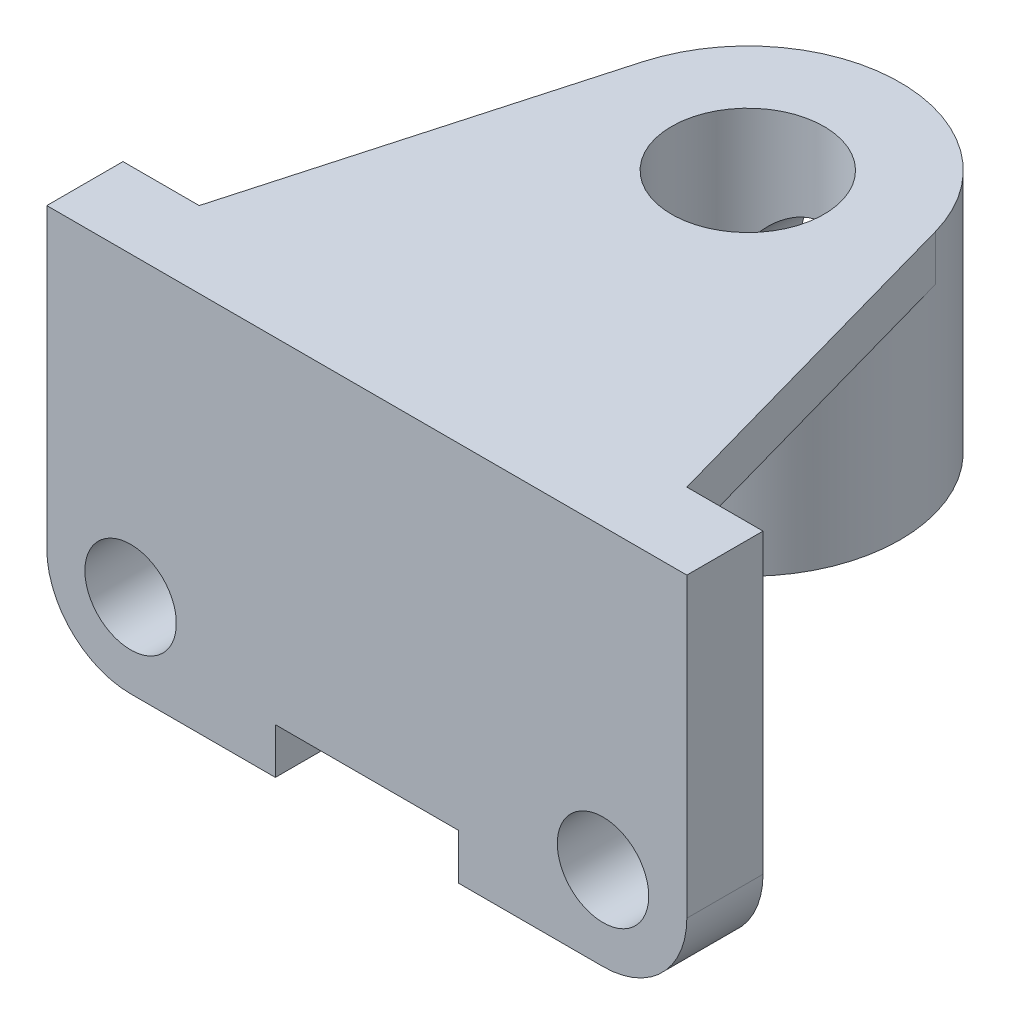
SolidWorks part; units mm, degrees
note: The reader was unsure of these and kept them because the rebuilt part matched: shared geometry of "草图2<3>".
ref_plane "前视基准面" through (0, 0, 0) normal (0, 0, 1) x (1, 0, 0)
ref_plane "上视基准面" through (0, 0, 0) normal (0, 1, 0) x (1, 0, 0)
ref_plane "右视基准面" through (0, 0, 0) normal (1, 0, 0) x (0, 0, -1)
other "Configuration Table"
sketch "草图1" plane through (0, 0, 0) normal (0, 0, 1) x (1, 0, 0)
  line L0 (0, 0) -> (0, -65.1314) construction
  line L1 (-31, -50) -> (-12, -50)
  line L2 (-42, -39) -> (-42, 0)
  line L3 (-42, 0) -> (42, 0)
  line L4 (42, -39) -> (42, 0)
  line L5 (12, -50) -> (31, -50)
  line L7 (-12, -50) -> (-12, -44)
  line L8 (-12, -44) -> (12, -44)
  line L9 (12, -50) -> (12, -44)
  arc A1 (31, -50) -> (42, -39) centre (31, -39) ccw
  arc A2 (-31, -50) -> (-42, -39) centre (-31, -39) cw
  circle A3 centre (31, -39) radius 6
  circle A4 centre (-31, -39) radius 6
  point P9 (42, -50)
  point P12 (-42, -50)
  dimension "D1" = 11
  dimension "D4" = 12
  dimension "D5" = 24
  dimension "D2" = 50
  dimension "D3" = 84
  dimension "D6" = 6
extrude "凸台-拉伸1" add sketch "草图1" along normal blind 10
sketch "草图2" plane through (0, 0, 0) normal (0, 1, 0) x (1, 0, 0)
  line L0 (0, 0) -> (0, 49.8021) construction
  line L1 (32, 0) -> (19.2559, 45.4047)
  line L2 (12, 0) -> (31, 0) construction
  line L3 (-32, 0) -> (-19.2559, 45.4047)
  line L4 (-12, 0) -> (12, 0) construction
  line L5 (-31, 0) -> (-12, 0) construction
  line L6 (12, 0) -> (32, 0)
  line L7 (-12, 0) -> (12, 0)
  line L8 (-32, 0) -> (-12, 0)
  line L9 (12, -10) -> (31, -10) construction
  line L10 (13.2288, 55) -> (-13.2288, 55)
  line L12 (3, 20.2263) -> (3, 0)
  line L13 (3, 0) -> (-3, 0)
  line L14 (-3, 20.2263) -> (-3, 0)
  circle A0 centre (0, 40) radius 10
  arc A1 (3, 20.2263) -> (-3, 20.2263) centre (0, 40) ccw
  dimension "D1" = 20
  dimension "D2" = 40
  dimension "D3" = 64
  dimension "D4" = 50
  dimension "D5" = 6
  dimension "D6" = 15
extrude "凸台-拉伸2" add sketch "草图2" against normal blind 6
extrude "凸台-拉伸3" add sketch "草图2<3>" against normal blind 32
sketch "草图2<3>" plane through (0, 0, 0) normal (0, 1, 0) x (1, 0, 0) same geometry as "草图2"
sketch "草图3" plane through (0, 0, -55) normal (0, 0, -1) x (-1, 0, 0)
  line L0 (13.2288, -6) -> (-13.2288, -32) construction
  circle A0 centre (0, -19) radius 8
  point P6 (0, -19)
  dimension "D1" = 16
extrude "切除-拉伸1" cut sketch "草图3" against normal up to next
